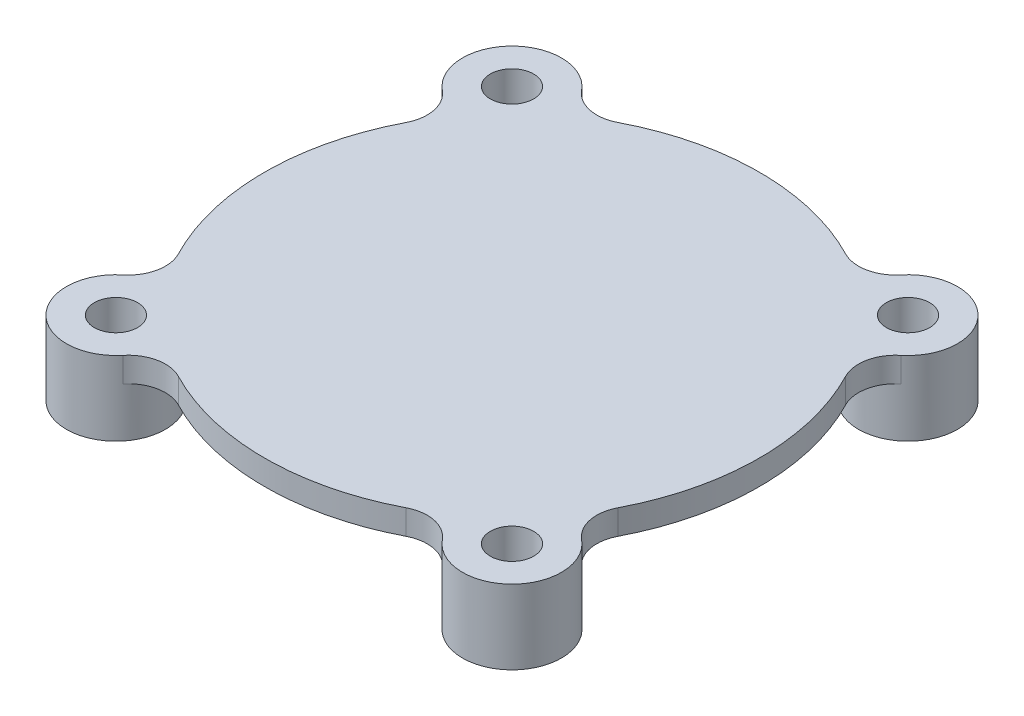
SolidWorks part; units mm, degrees
material "ABS PC"
ref_plane "Front Plane" through (0, 0, 0) normal (0, 0, 1) x (1, 0, 0)
ref_plane "Top Plane" through (0, 0, 0) normal (0, 1, 0) x (1, 0, 0)
ref_plane "Right Plane" through (0, 0, 0) normal (1, 0, 0) x (0, 0, -1)
sketch "Sketch1" plane through (0, 0, 0) normal (0, 1, 0) x (1, 0, 0)
  line L1 (-16, -16) -> (16, -16) construction
  line L2 (-16, -16) -> (-16, 16) construction
  line L3 (-16, 16) -> (16, 16) construction
  line L4 (16, -16) -> (16, 16) construction
  line L5 (-16, -16) -> (16, 16) construction
  line L6 (-16, 16) -> (16, -16) construction
  circle A0 centre (0, 0) radius 20
  circle A1 centre (-16, 16) radius 4
  circle A2 centre (16, 16) radius 4
  circle A3 centre (16, -16) radius 4
  circle A4 centre (-16, -16) radius 4
  point P8 (0, 0)
  dimension "D1" = 40
  dimension "D3" = 8
  dimension "D2" = 32
  dimension "D4" = 4
extrude "Boss-Extrude1" add sketch "Sketch1" along normal blind 2 contours A4 A0 A3 A2 A1 | A0 A1 | A0 A4 | A0 A3 | A0 A2 | A0 A1 | A0 A2 | A0 A3 | A0 A4 region at (0, 0, 0) region at (13.7201, 0, -13.7201) region at (16.2702, 0, -16.2702) region at (16.2702, 0, 16.2702) region at (13.7201, 0, 13.7201) region at (-13.7201, 0, -13.7201) region at (-16.2702, 0, -16.2702) region at (-16.2702, 0, 16.2702) region at (-13.7201, 0, 13.7201)
fillet "Fillet1" radius 3 8 edges at (-16, 1, 12) (-16, 1, -12) (12, 1, -16) (16, 1, -12) (16, 1, 12) (12, 1, 16) (-12, 1, 16) (-12, 1, -16)
extrude "Boss-Extrude2" add sketch "Sketch1<3>" against normal blind 4 contours A3 | A2 | A1 | A4
sketch "Sketch1<3>" plane through (0, 0, 0) normal (0, 1, 0) x (1, 0, 0) same geometry as "Sketch1"
hole_wizard "Ø3.5 (3.5) Diameter Hole1" positions "Sketch3" profile "Sketch4" hole size "Ø3.5" standard "ANSI Metric" end condition through all
sketch "Sketch3" plane through (0, 2, 0) normal (0, 1, 0) x (1, 0, 0)
  point P0 (-16, 16)
  point P3 (16, 16)
  point P6 (16, -16)
  point P9 (-16, -16)
sketch "Sketch4" plane through (-16, 2, -16) normal (1, 0, 0) x (0, 0, 1)
  line L0 (0, 0) -> (0, 6)
  line L1 (0, 6) -> (1.75, 6)
  line L2 (1.75, 6) -> (1.75, 0)
  line L5 (1.75, 0) -> (0, 0)
  line L11 (0, -6.35) -> (0, 107.95) construction
  dimension "Thru Hole Dia." = 3.5
  dimension "Thru Hole Depth" = 6
